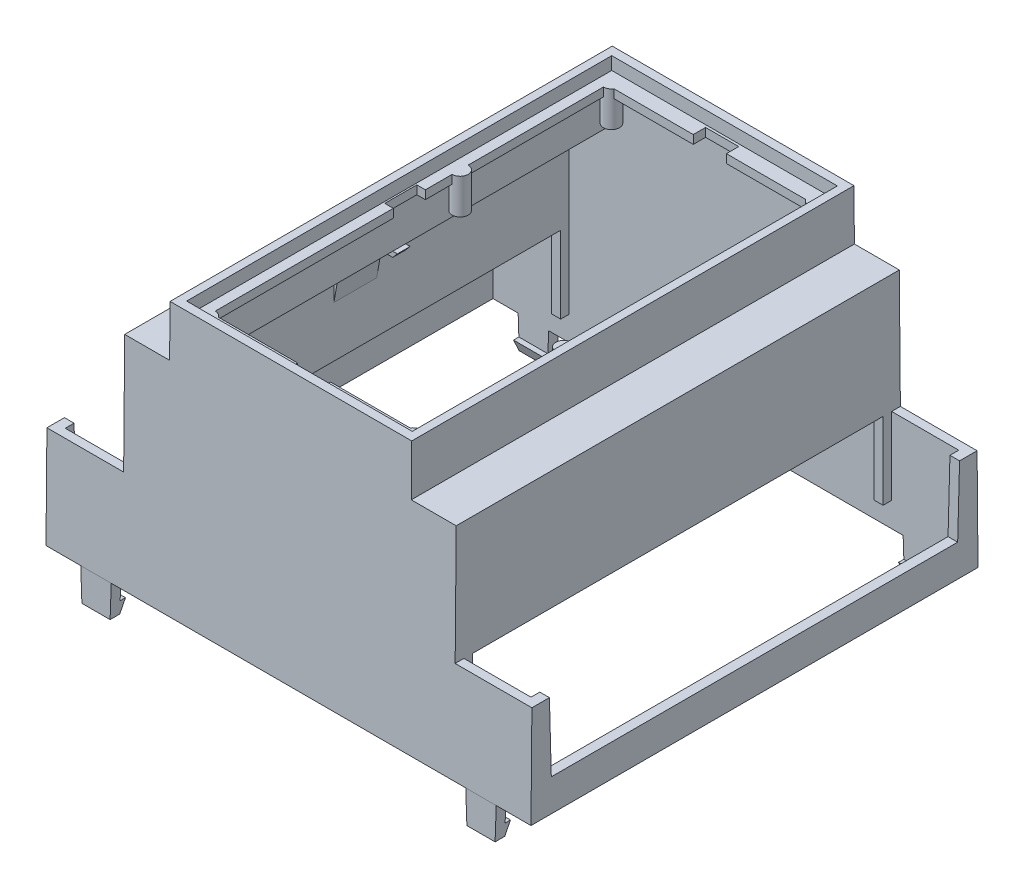
SolidWorks part; units mm, degrees
ref_plane "Спереди" through (0, 0, 0) normal (0, 0, 1) x (1, 0, 0)
ref_plane "Сверху" through (0, 0, 0) normal (0, 1, 0) x (1, 0, 0)
ref_plane "Справа" through (0, 0, 0) normal (1, 0, 0) x (0, 0, -1)
sketch "Эскиз2" plane through (0, 0, 0) normal (0, 0, 1) x (1, 0, 0)
  line L0 (-45.35, 0) -> (45.35, 0)
  line L1 (45.35, 0) -> (45.35, 25)
  line L2 (45.35, 25) -> (31, 25)
  line L3 (31, 25) -> (31, 47.2)
  line L4 (31, 47.2) -> (22.6, 47.2)
  line L5 (22.6, 47.2) -> (22.6, 56.7)
  line L6 (22.6, 56.7) -> (-22.6, 56.7)
  line L7 (-22.6, 56.7) -> (-22.6, 47.2)
  line L8 (-22.6, 47.2) -> (-31, 47.2)
  line L9 (-31, 47.2) -> (-31, 25)
  line L10 (-31, 25) -> (-45.35, 25)
  line L11 (-45.35, 25) -> (-45.35, 0)
  line L12 (0, 0) -> (0, 56.7) construction
  line L13 (-45.35, 6) -> (-38.85, 6)
  line L14 (-38.85, 6) -> (-38.6405, 0)
  line L15 (-33.3595, 0) -> (-33.15, 6)
  line L16 (-33.15, 6) -> (33.15, 6)
  line L17 (33.15, 6) -> (33.3595, 0)
  line L18 (38.6405, 0) -> (38.85, 6)
  line L19 (38.85, 6) -> (45.35, 6)
  line L20 (-36, 6) -> (-36, 0) construction
  dimension "D1" = 56.7
  dimension "D2" = 47.2
  dimension "D3" = 25
  dimension "D4" = 90.7
  dimension "D5" = 62
  dimension "D6" = 45.2
  dimension "D7" = 6
  dimension "D8" = 5.7
  dimension "D9" = 92
  dimension "D10" = 9.35
extrude "Бобышка-Вытянуть1" add sketch "Эскиз2" along normal mid plane 83.6 contours L18 L19 L1 L2 L3 L4 L5 L6 L7 L8 L9 L10 L11 L13 L14 L0 L15 L16 L17 region at (0, 27.5124, 0)
sketch "Эскиз3" plane through (0, 0, 0) normal (1, 0, 0) x (0, 0, -1)
  line L0 (-40, 10.6) -> (40, 10.6)
  line L1 (-41.8, 6) -> (41.8, 6) construction
  line L2 (40, 10.6) -> (40, 2.2)
  line L3 (40, 2.2) -> (39, 2.2)
  line L4 (39, 2.2) -> (40, 0)
  line L5 (-41.8, 0) -> (41.8, 0) construction
  line L6 (40, 0) -> (-40, 0)
  line L7 (-40, 0) -> (-39, 2.2)
  line L8 (-39, 2.2) -> (-40, 2.2)
  line L9 (-40, 2.2) -> (-40, 10.6)
  line L10 (0, 0) -> (0, 6) construction
  line L11 (-41.8, 0) -> (-41.8, 6) construction
  dimension "D1" = 1.8
  dimension "D2" = 3.8
  dimension "D3" = 2.8
  dimension "D4" = 4.6
extrude "Вырез-Вытянуть1" cut sketch "Эскиз3" against normal mid plane 87.1
sketch "Эскиз4" plane through (0, 25, 0) normal (0, 1, 0) x (1, 0, 0)
  line L0 (31, -41.8) -> (31, 41.8) construction
  line L1 (31, 40) -> (43.55, 40)
  line L2 (31, 40) -> (31, -40)
  line L3 (31, -40) -> (43.55, -40)
  line L4 (43.55, 40) -> (43.55, -40)
  line L5 (-31, -41.8) -> (-31, 41.8) construction
  line L6 (-31, 40) -> (-43.55, 40)
  line L7 (-31, 40) -> (-31, -40)
  line L8 (-31, -40) -> (-43.55, -40)
  line L9 (-43.55, 40) -> (-43.55, -40)
  line L10 (45.35, 41.8) -> (31, 41.8) construction
  line L11 (45.35, -41.8) -> (45.35, 41.8) construction
  line L12 (45.35, -41.8) -> (31, -41.8) construction
  line L13 (-31, 41.8) -> (-45.35, 41.8) construction
  line L14 (-31, -41.8) -> (-45.35, -41.8) construction
  line L15 (-45.35, -41.8) -> (-45.35, 41.8) construction
  dimension "D1" = 1.8
  dimension "D2" = 1.8
  dimension "D3" = 1.8
  dimension "D4" = 1.8
  dimension "D5" = 1.8
  dimension "D6" = 1.8
extrude "Вырез-Вытянуть2" cut sketch "Эскиз4" against normal up to surface (19 mm away) up to face at (0, 6, -40.9)
sketch "Эскиз5" plane through (0, 0, 0) normal (1, 0, 0) x (0, 0, -1)
  line L0 (-38.3518, 25) -> (-38, 12)
  line L1 (-41.8, 25) -> (41.8, 25) construction
  line L2 (-38, 12) -> (38, 12)
  line L3 (38, 12) -> (38.3518, 25)
  line L4 (38.3518, 25) -> (-38.3518, 25)
  line L5 (0, 6) -> (0, 47.2) construction
  line L6 (-41.8, 6) -> (41.8, 6) construction
  line L7 (-41.8, 47.2) -> (41.8, 47.2) construction
  dimension "D1" = 91.55
  dimension "D2" = 76
  dimension "D3" = 6
extrude "Вырез-Вытянуть3" cut sketch "Эскиз5" against normal mid plane 92
sketch "Эскиз6" plane through (0, 10.6, 0) normal (0, -1, 0) x (1, 0, 0)
  line L0 (-31, 40) -> (-31, -40) construction
  line L1 (-31, -38.4) -> (31, -38.4)
  line L2 (-31, -38.4) -> (-31, 38.4)
  line L3 (-31, 38.4) -> (31, 38.4)
  line L4 (31, -38.4) -> (31, 38.4)
  line L5 (31, -40) -> (31, 40) construction
  line L6 (-33.15, 41.8) -> (33.15, 41.8) construction
  line L7 (-33.15, -41.8) -> (33.15, -41.8) construction
  dimension "D1" = 3.4
  dimension "D2" = 3.4
extrude "Вырез-Вытянуть4" cut sketch "Эскиз6" against normal up to surface (14.4 mm away) up to face at (0, 25, 0)
sketch "Эскиз7" plane through (0, 10.6, 0) normal (0, -1, 0) x (1, 0, 0)
  line L0 (33.15, -40) -> (-33.15, -40) construction
  line L1 (-29.3, -40) -> (29.3, -40)
  line L2 (-29.3, -40) -> (-29.3, 40)
  line L3 (-29.3, 40) -> (29.3, 40)
  line L4 (29.3, -40) -> (29.3, 40)
  line L5 (-33.15, 40) -> (33.15, 40) construction
  line L6 (-31, -38.4) -> (-31, 38.4) construction
  line L7 (31, 38.4) -> (31, -38.4) construction
  dimension "D1" = 1.7
  dimension "D2" = 1.7
extrude "Вырез-Вытянуть5" cut sketch "Эскиз7" against normal up to surface (14.4 mm away) up to face at (0, 25, 0)
sketch "Эскиз8" plane through (0, 25, 0) normal (0, -1, 0) x (1, 0, 0)
  line L1 (-29.3, -40) -> (29.3, -40)
  line L2 (-29.3, -40) -> (-29.3, 40)
  line L3 (-29.3, 40) -> (29.3, 40)
  line L4 (29.3, -40) -> (29.3, 40)
extrude "Вырез-Вытянуть6" cut sketch "Эскиз8" against normal blind 20.5
sketch "Эскиз9" plane through (0, 45.5, 0) normal (0, -1, 0) x (1, 0, 0)
  line L0 (33.15, -40) -> (-33.15, -40) construction
  line L1 (-21.1, -40) -> (21.1, -40)
  line L2 (-21.1, -40) -> (-21.1, 40)
  line L3 (-21.1, 40) -> (21.1, 40)
  line L4 (21.1, -40) -> (21.1, 40)
  line L5 (-33.15, 40) -> (33.15, 40) construction
  line L6 (0, -40) -> (0, 40) construction
  line L7 (-22.6, 41.8) -> (-22.6, -41.8) construction
  dimension "D1" = 1.5
extrude "Вырез-Вытянуть7" cut sketch "Эскиз9" against normal blind 7.2 contours L4 L3 L2 L1
sketch "Эскиз16" plane through (0, 0, 0) normal (1, 0, 0) x (0, 0, -1)
  line L0 (0, 0) -> (0, 56.7) construction
  line L1 (-41.8, 56.7) -> (41.8, 56.7) construction
  line L2 (-41.8, 56.7) -> (-41.8, 6)
  line L3 (-41.8, 6) -> (-41.35, 56.7)
  line L4 (-41.35, 56.7) -> (-41.8, 56.7)
  line L5 (41.35, 56.7) -> (41.8, 56.7)
  line L6 (41.8, 56.7) -> (41.8, 6)
  line L7 (41.8, 6) -> (41.35, 56.7)
  dimension "D1" = 82.7
extrude "Вырез-Вытянуть10" cut sketch "Эскиз16" against normal mid plane 92
sketch "Эскиз10" plane through (0, 56.7, 0) normal (0, 1, 0) x (1, 0, 0)
  line L0 (22.6, -41.35) -> (22.6, 41.35) construction
  line L1 (21.1, 39.75) -> (-21.1, 39.75)
  line L2 (21.1, 39.75) -> (21.1, -39.75)
  line L3 (21.1, -39.75) -> (-21.1, -39.75)
  line L4 (-21.1, 39.75) -> (-21.1, -39.75)
  line L5 (-22.6, -41.35) -> (-22.6, 41.35) construction
  line L8 (-22.6, 41.35) -> (22.6, 41.35) construction
  line L9 (-22.6, -41.35) -> (22.6, -41.35) construction
  dimension "D1" = 1.5
  dimension "D2" = 1.5
  dimension "D3" = 1.6
  dimension "D4" = 1.6
extrude "Вырез-Вытянуть8" cut sketch "Эскиз10" against normal blind 2.4
sketch "Эскиз11" plane through (0, 54.3, 0) normal (0, 1, 0) x (1, 0, 0)
  line L0 (-3.1, 39.3) -> (3.1, 39.3)
  line L1 (3.1, 39.3) -> (3.1, 37)
  line L2 (3.1, 37) -> (19.2, 37)
  line L3 (19.2, 37) -> (19.2, 3)
  line L4 (19.2, 3) -> (20.8, 3)
  line L5 (20.8, 3) -> (20.8, -3)
  line L6 (20.8, -3) -> (19.2, -3)
  line L7 (19.2, -3) -> (19.2, -37)
  line L8 (19.2, -37) -> (3.1, -37)
  line L9 (3.1, -37) -> (3.1, -39.3)
  line L10 (3.1, -39.3) -> (-3.1, -39.3)
  line L11 (-3.1, -39.3) -> (-3.1, -37)
  line L12 (-3.1, -37) -> (-19.2, -37)
  line L13 (-19.2, -37) -> (-19.2, -3)
  line L14 (-19.2, -3) -> (-20.8, -3)
  line L15 (-20.8, -3) -> (-20.8, 3)
  line L16 (-20.8, 3) -> (-19.2, 3)
  line L17 (-19.2, 3) -> (-19.2, 37)
  line L18 (-19.2, 37) -> (-3.1, 37)
  line L19 (-3.1, 37) -> (-3.1, 39.3)
  line L20 (21.1, 0) -> (-21.1, 0) construction
  line L21 (21.1, -39.75) -> (21.1, 39.75) construction
  line L22 (-21.1, 39.75) -> (-21.1, -39.75) construction
  line L23 (0, 39.75) -> (0, -39.75) construction
  line L24 (21.1, 39.75) -> (-21.1, 39.75) construction
  line L25 (-21.1, -39.75) -> (21.1, -39.75) construction
  dimension "D1" = 38.4
  dimension "D2" = 41.6
  dimension "D3" = 74
  dimension "D4" = 78.6
  dimension "D5" = 6
  dimension "D6" = 6.2
extrude "Вырез-Вытянуть9" cut sketch "Эскиз11" against normal blind 2.4
sketch "Эскиз12" plane through (0, 0, 0) normal (0, 0, 1) x (1, 0, 0)
  line L0 (-29.3, 45.5) -> (-29.3, 44.5)
  line L1 (-29.3, 45.5) -> (-29.3, 10.6) construction
  line L2 (-29.3, 44.5) -> (-21.1, 44.5)
  line L3 (-21.1, 44.5) -> (-20.25, 45.5)
  line L4 (-20.25, 45.5) -> (-29.3, 45.5)
  line L5 (29.3, 45.5) -> (20.25, 45.5)
  line L6 (20.25, 45.5) -> (21.1, 44.5)
  line L7 (21.1, 44.5) -> (29.3, 44.5)
  line L8 (29.3, 45.5) -> (29.3, 10.6) construction
  line L9 (29.3, 44.5) -> (29.3, 45.5)
  line L10 (0, 56.7) -> (0, 6) construction
  line L11 (21.1, 56.7) -> (-21.1, 56.7) construction
  line L12 (33.15, 6) -> (-33.15, 6) construction
  dimension "D1" = 1
  dimension "D2" = 40.5
  dimension "D3" = 8.2
extrude "Бобышка-Вытянуть2" add sketch "Эскиз12" along normal mid plane 2.4
sketch "Эскиз13" plane through (0, 0, 0) normal (0, 0, 1) x (1, 0, 0)
  line L0 (-29.3, 34.5) -> (-28.5, 39.1)
  line L1 (-29.3, 45.5) -> (-29.3, 10.6) construction
  line L2 (-28.5, 39.1) -> (-29.3, 39.1)
  line L3 (-29.3, 39.1) -> (-29.3, 34.5)
  line L4 (29.3, 39.1) -> (28.5, 39.1)
  line L5 (29.3, 45.5) -> (29.3, 10.6) construction
  line L6 (28.5, 39.1) -> (29.3, 34.5)
  line L7 (29.3, 34.5) -> (29.3, 39.1)
  line L8 (0, 52.7) -> (0, 6) construction
  line L9 (-3.1, 52.7) -> (3.1, 52.7) construction
  line L10 (33.15, 6) -> (-33.15, 6) construction
  line L12 (-20.25, 45.5) -> (-21.1, 45.5) construction
  dimension "D1" = 6.4
  dimension "D2" = 0.8
  dimension "D3" = 11
extrude "Бобышка-Вытянуть3" add sketch "Эскиз13" along normal mid plane 8
sketch "Эскиз14" plane through (0, 45.5, 0) normal (0, -1, 0) x (1, 0, 0)
  line L0 (0, 0) -> (-29.3, 0) construction
  line L1 (-29.3, 38.4) -> (-29.3, -38.4) construction
  line L2 (0, 0) -> (0, 40) construction
  line L3 (-33.15, 40) -> (33.15, 40) construction
  line L4 (33.15, -40) -> (-33.15, -40) construction
  line L5 (-27.5, -37) -> (27.5, -37) construction
  line L6 (-27.5, -37) -> (-27.5, 37) construction
  line L7 (-27.5, 37) -> (27.5, 37) construction
  line L8 (27.5, -37) -> (27.5, 37) construction
  circle A0 centre (-27.5, -37) radius 1.3
  circle A1 centre (-27.5, 37) radius 1.3
  circle A2 centre (27.5, -37) radius 1.3
  circle A3 centre (27.5, 37) radius 1.3
  dimension "D3" = 2.6
  dimension "D1" = 3
  dimension "D2" = 1.8
extrude "Бобышка-Вытянуть4" add sketch "Эскиз14" along normal blind 4.4 draft 3
sketch "Эскиз15" plane through (0, 54.3, 0) normal (0, 1, 0) x (1, 0, 0)
  line L0 (-20.25, 0) -> (20.25, 0) construction
  line L1 (19.2, 37.8) -> (-19.2, 37.8) construction
  line L2 (19.2, 37.8) -> (19.2, -37.8) construction
  line L3 (19.2, -37.8) -> (-19.2, -37.8) construction
  line L4 (-19.2, 37.8) -> (-19.2, -37.8) construction
  line L5 (-20.25, -1.2) -> (-20.25, 1.2) construction
  line L6 (20.25, -1.2) -> (20.25, 1.2) construction
  line L7 (0, 39.3) -> (0, -39.3) construction
  line L8 (3.1, 39.3) -> (-3.1, 39.3) construction
  line L9 (-3.1, -39.3) -> (3.1, -39.3) construction
  line L10 (19.2, 3) -> (19.2, 37) construction
  line L12 (-21.1, 40) -> (21.1, 40) construction
  circle A0 centre (19.2, 37.8) radius 1.5
  circle A1 centre (-19.2, 37.8) radius 1.5
  circle A2 centre (-19.2, -37.8) radius 1.5
  circle A3 centre (19.2, -37.8) radius 1.5
  circle A4 centre (19.2, -9.5) radius 1.5
  circle A5 centre (-19.2, 9.5) radius 1.5
  dimension "D2" = 3
  dimension "D1" = 2.2
  dimension "D3" = 9.5
  dimension "D4" = 9.5
extrude "Бобышка-Вытянуть5" add sketch "Эскиз15" against normal blind 6.6
